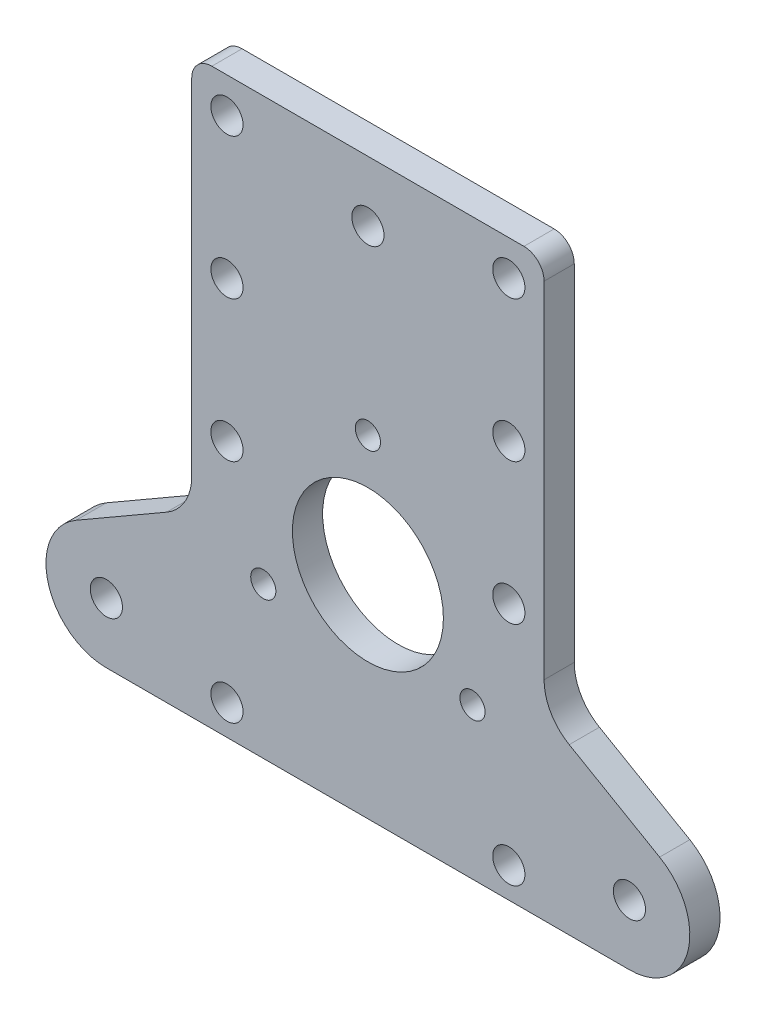
SolidWorks part; units mm, degrees
material "6061 Alloy"
ref_plane "Front" through (0, 0, 0) normal (0, 0, 1) x (1, 0, 0)
ref_plane "Top" through (0, 0, 0) normal (0, 1, 0) x (1, 0, 0)
ref_plane "Right" through (0, 0, 0) normal (1, 0, 0) x (0, 0, -1)
sketch "Tool Ball Pattern" plane through (0, 0, 0) normal (0, 0, 1) x (1, 0, 0)
  line L0 (0, 0) -> (0, 30) construction
  line L1 (0, 0) -> (-25.9808, -15) construction
  line L2 (0, 0) -> (25.9808, -15) construction
  line L4 (-6, -1) -> (6, -1)
  line L5 (-6, -1) -> (-6, 1)
  line L6 (-6, 1) -> (6, 1)
  line L7 (6, -1) -> (6, 1)
  line L8 (-6, -1) -> (6, 1) construction
  line L9 (-6, 1) -> (6, -1) construction
  circle A0 centre (0, 0) radius 2.5
  circle A1 centre (0, 30) radius 4
  circle A2 centre (25.9808, -15) radius 4
  circle A3 centre (-25.9808, -15) radius 4
  circle A4 centre (0, 12) radius 1.25
  circle A5 centre (-10.3923, -6) radius 1.25
  circle A6 centre (10.3923, -6) radius 1.25
  circle A7 centre (0, 0) radius 7.5
  dimension "D4" = 5
  dimension "D7" = 8
  dimension "D8" = 12
  dimension "D9" = 12
  dimension "D10" = 12
  dimension "D11" = 2.5
  dimension "D12" = 15
  dimension "D1" = 30
  dimension "D2" = 120
  dimension "D3" = 120
  dimension "D5" = 12
  dimension "D6" = 2
sketch "Parking Post Dowel Region" plane through (0, 0, 0) normal (0, 0, 1) x (1, 0, 0)
  line L0 (0, 35.5) -> (15, 35.5) construction
  line L1 (0, 0) -> (0, 30) construction
  line L2 (0, 35.5) -> (-15, 35.5) construction
  line L3 (17.5, 35.5) -> (45, 35.5) construction
  line L4 (17.5, 38) -> (45, 38)
  line L5 (17.5, 33) -> (45, 33)
  line L6 (0, 0) -> (0, 30) construction
  line L7 (-17.5, 35.5) -> (-45, 35.5) construction
  line L8 (-17.5, 38) -> (-45, 38)
  line L9 (-17.5, 33) -> (-45, 33)
  line L10 (0, 22.5) -> (15, 22.5) construction
  line L11 (0, 22.5) -> (-15, 22.5) construction
  line L12 (45, 22.5) -> (17.5, 22.5) construction
  line L13 (45, 20) -> (17.5, 20)
  line L14 (45, 25) -> (17.5, 25)
  line L15 (-45, 22.5) -> (-17.5, 22.5) construction
  line L16 (-45, 20) -> (-17.5, 20)
  line L17 (-45, 25) -> (-17.5, 25)
  line L19 (-51.1267, -10.5) -> (51.1267, -10.5)
  line L20 (-51.1267, -10.5) -> (-51.1267, 9.5)
  line L21 (-51.1267, 9.5) -> (51.1267, 9.5)
  line L22 (51.1267, -10.5) -> (51.1267, 9.5)
  line L23 (-51.1267, -10.5) -> (51.1267, 9.5) construction
  line L24 (-51.1267, 9.5) -> (51.1267, -10.5) construction
  arc A0 (17.5, 38) -> (17.5, 33) centre (17.5, 35.5) ccw
  arc A1 (45, 33) -> (45, 38) centre (45, 35.5) ccw
  arc A2 (-17.5, 38) -> (-17.5, 33) centre (-17.5, 35.5) cw
  arc A3 (-45, 33) -> (-45, 38) centre (-45, 35.5) cw
  arc A4 (45, 20) -> (45, 25) centre (45, 22.5) ccw
  arc A5 (17.5, 25) -> (17.5, 20) centre (17.5, 22.5) ccw
  arc A6 (-45, 20) -> (-45, 25) centre (-45, 22.5) cw
  arc A7 (-17.5, 25) -> (-17.5, 20) centre (-17.5, 22.5) cw
  point P8 (31.25, 35.5)
  point P13 (15, 35.5)
  point P16 (-31.25, 35.5)
  point P25 (31.25, 22.5)
  point P31 (15, 22.5)
  point P32 (0, -0.5)
  point P37 (-31.25, 22.5)
  dimension "D3" = 2.5
  dimension "D1" = 26
  dimension "D2" = 35
  dimension "D4" = 27.5
  dimension "D5" = 90
  dimension "D6" = 13
  dimension "D7" = 20
  dimension "D8" = 9.5
sketch "Side View Boundaries" plane through (0, 0, 0) normal (1, 0, 0) x (0, 0, -1)
  line L0 (3.6, -10) -> (0, -10)
  line L1 (3.6, -10) -> (3.6, 16)
  line L2 (0, -10) -> (0, 16)
  line L3 (3.6, 16) -> (0, 16)
  line L4 (3.6, -10) -> (0, 16) construction
  line L5 (0, -10) -> (3.6, 16) construction
  line L6 (3.6, -10) -> (3.6, -32)
  line L7 (3.6, -32) -> (36.6, -32)
  line L8 (36.6, -32) -> (36.6, -63.6242)
  line L9 (36.6, -63.6242) -> (-46.4, -63.6242)
  line L10 (-46.4, -63.6242) -> (-46.4, 115.7014)
  line L11 (-46.4, 115.7014) -> (41.8, 115.7014)
  line L12 (41.8, 115.7014) -> (41.8, 39)
  line L13 (41.8, 39) -> (3.6, 39)
  line L14 (3.6, 39) -> (3.6, 16)
  line L15 (-4.4, -7.5) -> (0, -7.5)
  line L16 (-4.4, -7.5) -> (-4.4, 7.5)
  line L17 (0, -7.5) -> (0, 7.5)
  line L18 (-4.4, 7.5) -> (0, 7.5)
  line L19 (-4.4, -7.5) -> (0, 7.5) construction
  line L20 (0, -7.5) -> (-4.4, 7.5) construction
  line L21 (0, 0) -> (-2.2, 0) construction
  line L22 (3.6, -32) -> (-46.4, -32) construction
  point P1 (1.8, 3)
  point P2 (0, 0)
  point P16 (-2.2, 0)
  dimension "D1" = 3.6
  dimension "D2" = 26
  dimension "D3" = 38.2
  dimension "D4" = 32
  dimension "D5" = 50
  dimension "D6" = 8
  dimension "D7" = 15
  dimension "D8" = 33
  dimension "D9" = 39
  dimension "D10" = 4
ref_plane "Plane1" through (0, 30, 0) normal (0, 1, 0) x (1, 0, 0)
sketch "Tool Tip Center Limits" plane through (0, 0, 0) normal (1, 0, 0) x (0, 0, -1)
  line L0 (-24.132, 115.7014) -> (-24.132, -63.6242) construction
  line L1 (3.6, -10) -> (3.6, 16) construction
  line L2 (36.6, -63.6242) -> (-46.4, -63.6242) construction
  line L3 (-46.4, 115.7014) -> (41.8, 115.7014) construction
  line L4 (-26.632, -63.6242) -> (-26.632, 115.7014) construction
  dimension "D1" = 27.732
  dimension "D2" = 2.5
sketch "Tool Balls Side View" plane through (0, 0, 0) normal (1, 0, 0) x (0, 0, -1)
  line L0 (3.9, 30) -> (0, 30) construction
  line L1 (0, 34) -> (0, 26) construction
  line L2 (3.9, 30) -> (3.9, 34) construction
  line L3 (3.9, -15) -> (0, -15) construction
  line L4 (0, -11) -> (0, -19) construction
  line L5 (3.6, 39) -> (3.6, 16) construction
  circle A0 centre (3.9, 30) radius 4
  circle A1 centre (3.9, -15) radius 4
  dimension "D2" = 8
  dimension "D1" = 0.3
ref_plane "Plane2" through (0, -15, 0) normal (0, -1, 0) x (-1, 0, 0)
sketch "Tool Balls Top View" plane through (0, -15, 0) normal (0, -1, 0) x (-1, 0, 0)
  line L0 (-25.9808, 3.9) -> (-25.9808, 0) construction
  line L1 (-29.9808, 0) -> (-21.9808, 0) construction
  line L2 (0, 3.9) -> (-25.9808, 3.9) construction
  line L3 (0, -46.4) -> (0, 41.8) construction
  line L4 (0, 3.9) -> (0, 0) construction
  circle A0 centre (-25.9808, 3.9) radius 4
  circle A1 centre (25.9808, 3.9) radius 4
  circle A2 centre (0, 3.9) radius 4
  dimension "D1" = 8
ref_plane "Plane3" through (0, 0, 0) normal (0, 0, 1) x (1, 0, 0)
sketch "Sketch3" plane through (0, 0, 0) normal (1, 0, 0) x (0, 0, -1)
  line L1 (0, 34) -> (0, 26) construction
  line L2 (0, 30) -> (0, 31.6) construction
  line L3 (0, 30) -> (3.9, 30) construction
  line L4 (3.9, 30) -> (0, 30) construction
  line L5 (0, 31.6) -> (0.2339, 31.6)
  line L6 (3.6, 39) -> (3.6, 16) construction
  line L8 (3.6, 33.9887) -> (3.6, 35.9887)
  line L9 (3.6, 35.9887) -> (0, 35.9887)
  line L10 (0, 50) -> (0, -50) construction
  line L11 (0, 35.9887) -> (0, 31.6)
  circle A0 centre (3.9, 30) radius 4 construction
  arc A1 (0.2339, 31.6) -> (3.6, 33.9887) centre (3.9, 30) cw
  dimension "D1" = 1.6
  dimension "D2" = 2
revolve "Revolve1" add sketch "Sketch3" angle 360 about L3
chamfer "Chamfer1" distance 1 angle 70 1 edges at (5.9887, 30, -3.6) first distance on face at (5.9887, 30, -3.6)
pattern_circular "CirPattern2" count 3 over 360 about axis through (0, 0, 0) along (0, 0, 1) reverse direction yes of bodies 164
sketch "Sketch1" plane through (0, 0, 0) normal (0, 0, 1) x (1, 0, 0)
  line L0 (21.9808, -15) -> (29.9808, -15) construction
  line L1 (25.9808, -21) -> (-25.9808, -21)
  line L2 (-28.9808, -9.8038) -> (-17.5, -3.1754)
  line L3 (17.5, 36) -> (17.5, -3.1754)
  line L4 (28.9808, -9.8038) -> (17.5, -3.1754)
  line L5 (17.5, 36) -> (-17.5, 36)
  line L6 (-17.5, 36) -> (-17.5, -3.1754)
  line L7 (0, 0) -> (0, 53.3702) construction
  line L8 (0, -63.6242) -> (0, 115.7014) construction
  line L9 (0, 0) -> (-25.9808, -15) construction
  circle A0 centre (-25.9808, -15) radius 6 construction
  circle A1 centre (25.9808, -15) radius 6 construction
  circle A2 centre (0, 30) radius 6 construction
  arc A3 (-28.9808, -9.8038) -> (-25.9808, -21) centre (-25.9808, -15) ccw
  arc A4 (25.9808, -21) -> (28.9808, -9.8038) centre (25.9808, -15) ccw
  dimension "D1" = 12
  dimension "D2" = 36
  dimension "D3" = 35
extrude "Boss-Extrude1" add sketch "Sketch1" along normal blind 3 separate body
sketch "Sketch4" plane through (0, 0, 3) normal (0, 0, 1) x (1, 0, 0)
  circle A0 centre (0, 0) radius 7.5 construction
  circle A1 centre (0, 0) radius 7.5
extrude "Cut-Extrude1" cut sketch "Sketch4" against normal through all
hole_wizard "M3x0.5 Tapped Hole2" positions "Sketch5" profile "Sketch6" tap size "M3x0.5" standard "ANSI Metric" end condition through all
sketch "Sketch5" plane through (0, 0, 0) normal (0, 0, -1) x (-1, 0, 0)
  point P0 (10.3923, -6)
  point P3 (0, 12)
  point P6 (-10.3923, -6)
sketch "Sketch6" plane through (-10.3923, -6, 0) normal (1, 0, 0) x (0, 1, 0)
  line L0 (0, 0) -> (0, 3)
  line L1 (0, 3) -> (1.25, 3)
  line L2 (1.25, 3) -> (1.25, 0)
  line L5 (1.25, 0) -> (0, 0)
  line L11 (0, -6.35) -> (0, 107.95) construction
  dimension "Thru Tap Drill Dia." = 2.5
  dimension "Thru Tap Drill Depth" = 3
cosmetic thread "Hole Thread1" parameters "D2"=3
cosmetic thread "Hole Thread2" parameters "D2"=3
cosmetic thread "Hole Thread3" parameters "D2"=3
fillet "Fillet1" radius 5 2 edges at (17.5, -3.1754, 1.5) (-17.5, -3.1754, 1.5)
fillet "Fillet2" radius 2 2 edges at (-17.5, 36, 1.5) (17.5, 36, 1.5)
hole_wizard "M3 Clearance Hole3" positions "Sketch8" profile "Sketch9" hole size "M3" standard "ANSI Metric" end condition through all
sketch "Sketch8" plane through (0, 0, 3) normal (0, 0, 1) x (1, 0, 0)
  line L0 (14, 36) -> (14, -21) construction
  line L1 (15.5, 36) -> (-15.5, 36) construction
  line L2 (-25.9808, -21) -> (25.9808, -21) construction
  line L5 (17.5, -0.2887) -> (17.5, 34) construction
  line L7 (0, -21) -> (0, 36) construction
  point P0 (14, 32.5)
  point P2 (14, 18.5)
  point P4 (14, 4.5)
  point P8 (14, -18)
  point P35 (-14, -18)
  point P37 (-14, 4.5)
  point P38 (-14, 18.5)
  point P39 (-14, 32.5)
  dimension "D1" = 3.5
  dimension "D3" = 3.5
  dimension "D4" = 14
  dimension "D5" = 14
  dimension "D6" = 3
sketch "Sketch9" plane through (14, 32.5, 3) normal (1, 0, 0) x (0, -1, 0)
  line L0 (0, 0) -> (0, 6.6)
  line L1 (0, 6.6) -> (1.6, 6.6)
  line L2 (1.6, 6.6) -> (1.6, 0)
  line L5 (1.6, 0) -> (0, 0)
  line L11 (0, -6.35) -> (0, 107.95) construction
  dimension "Thru Hole Dia." = 3.2
  dimension "Thru Hole Depth" = 6.6
hole_wizard "M3 Clearance Hole2" positions "Sketch12" profile "Sketch13" hole size "M3" standard "ANSI Metric" end condition through all
sketch "Sketch12" plane through (0, 0, 3) normal (0, 0, 1) x (1, 0, 0)
  point P0 (0, 30)
  point P3 (25.9808, -15)
  point P5 (-25.9808, -15)
sketch "Sketch13" plane through (0, 30, 3) normal (1, 0, 0) x (0, -1, 0)
  line L0 (0, 0) -> (0, 6.6)
  line L1 (0, 6.6) -> (1.6, 6.6)
  line L2 (1.6, 6.6) -> (1.6, 0)
  line L5 (1.6, 0) -> (0, 0)
  line L11 (0, -6.35) -> (0, 107.95) construction
  dimension "Thru Hole Dia." = 3.2
  dimension "Thru Hole Depth" = 6.6
chamfer "Chamfer2" distance 0.4 angle 45 2 edges at (22.9864, -20.1864, 0) (25.1808, -16.3856, 0)
chamfer "Chamfer3" distance 0.4 angle 45 2 edges at (5.9887, 30, 0) (1.6, 30, 0)
chamfer "Chamfer4" distance 0.4 angle 45 2 edges at (-28.9751, -9.8136, 0) (-26.7808, -13.6144, 0)
sketch "Sketch14" plane through (0, 0, 0) normal (0, 0, -1) x (-1, 0, 0)
  line L0 (-14, 32.5) -> (-14, 30.5) construction
  line L1 (-12.4, 32.5) -> (-12.4, 30.5)
  line L2 (-15.6, 32.5) -> (-15.6, 30.5)
  line L3 (14, 32.5) -> (14, 30.5) construction
  line L4 (15.6, 32.5) -> (15.6, 30.5)
  line L5 (12.4, 32.5) -> (12.4, 30.5)
  line L6 (14, 18.5) -> (14, 16.5) construction
  line L7 (15.6, 18.5) -> (15.6, 16.5)
  line L8 (12.4, 18.5) -> (12.4, 16.5)
  line L9 (-14, 18.5) -> (-14, 16.5) construction
  line L10 (-12.4, 18.5) -> (-12.4, 16.5)
  line L11 (-15.6, 18.5) -> (-15.6, 16.5)
  line L12 (-14, 4.5) -> (-14, 2.5) construction
  line L13 (-12.4, 4.5) -> (-12.4, 2.5)
  line L14 (-15.6, 4.5) -> (-15.6, 2.5)
  line L15 (14, 4.5) -> (14, 2.5) construction
  line L16 (15.6, 4.5) -> (15.6, 2.5)
  line L17 (12.4, 4.5) -> (12.4, 2.5)
  line L18 (-14, -18) -> (-14, -16) construction
  line L19 (-15.6, -18) -> (-15.6, -16)
  line L20 (-12.4, -18) -> (-12.4, -16)
  line L21 (14, -18) -> (14, -16) construction
  line L22 (12.4, -18) -> (12.4, -16)
  line L23 (15.6, -18) -> (15.6, -16)
  arc A0 (-12.4, 32.5) -> (-15.6, 32.5) centre (-14, 32.5) ccw
  arc A1 (-15.6, 30.5) -> (-12.4, 30.5) centre (-14, 30.5) ccw
  arc A2 (15.6, 32.5) -> (12.4, 32.5) centre (14, 32.5) ccw
  arc A3 (12.4, 30.5) -> (15.6, 30.5) centre (14, 30.5) ccw
  arc A4 (15.6, 18.5) -> (12.4, 18.5) centre (14, 18.5) ccw
  arc A5 (12.4, 16.5) -> (15.6, 16.5) centre (14, 16.5) ccw
  arc A6 (-12.4, 18.5) -> (-15.6, 18.5) centre (-14, 18.5) ccw
  arc A7 (-15.6, 16.5) -> (-12.4, 16.5) centre (-14, 16.5) ccw
  arc A8 (-12.4, 4.5) -> (-15.6, 4.5) centre (-14, 4.5) ccw
  arc A9 (-15.6, 2.5) -> (-12.4, 2.5) centre (-14, 2.5) ccw
  arc A10 (15.6, 4.5) -> (12.4, 4.5) centre (14, 4.5) ccw
  arc A11 (12.4, 2.5) -> (15.6, 2.5) centre (14, 2.5) ccw
  arc A12 (-15.6, -18) -> (-12.4, -18) centre (-14, -18) ccw
  arc A13 (-12.4, -16) -> (-15.6, -16) centre (-14, -16) ccw
  arc A14 (12.4, -18) -> (15.6, -18) centre (14, -18) ccw
  arc A15 (15.6, -16) -> (12.4, -16) centre (14, -16) ccw
  point P3 (-14, 31.5)
  point P8 (14, 31.5)
  point P16 (14, 17.5)
  point P24 (-14, 17.5)
  point P32 (-14, 3.5)
  point P40 (14, 3.5)
  point P48 (-14, -17)
  point P56 (14, -17)
  dimension "D2" = 1.6
  dimension "D1" = 2
extrude "2mm Slots" [suppressed] cut sketch "Sketch14" against normal through all
delete or keep bodies "Body-Delete/Keep 1" [suppressed] type keep bodies bodies 164
delete or keep bodies "Body-Delete/Keep 2" type keep bodies bodies 170
equation "\"base_tool_plate_width\"= 36"
equation "\"D3@Sketch8\"=\"D1@Sketch8\""
